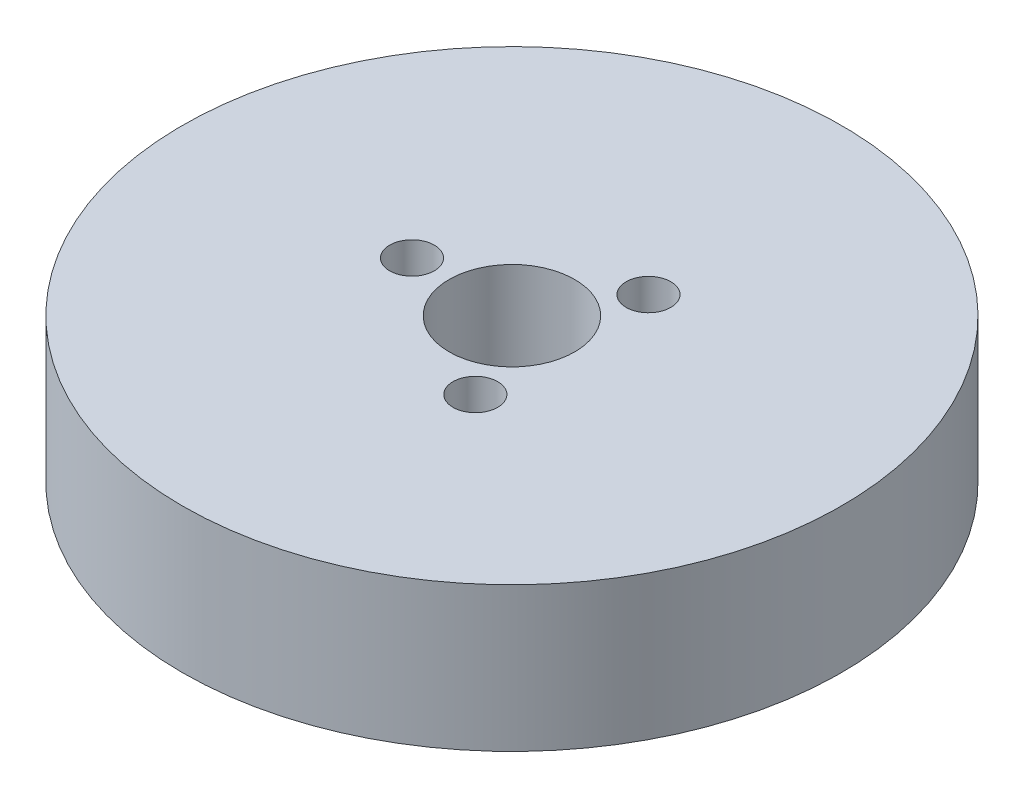
SolidWorks part; units mm, degrees
ref_plane "Front Plane" through (0, 0, 0) normal (0, 0, 1) x (1, 0, 0)
ref_plane "Top Plane" through (0, 0, 0) normal (0, 1, 0) x (1, 0, 0)
ref_plane "Right Plane" through (0, 0, 0) normal (1, 0, 0) x (0, 0, -1)
sketch "Sketch1" plane through (0, 0, 0) normal (0, 1, 0) x (1, 0, 0)
  circle A0 centre (0, 0) radius 52.5
  dimension "FLANGE_OD" = 105
extrude "Boss-Extrude1" add sketch "Sketch1" along normal blind 23
sketch "Sketch2" plane through (0, 0, 0) normal (0, 1, 0) x (1, 0, 0)
  circle A0 centre (0, 0) radius 10
  dimension "BORE_D" = 20
extrude "Cut-Extrude1" cut sketch "Sketch2" along normal through all
sketch "Sketch3" plane through (0, 23, 0) normal (0, 1, 0) x (1, 0, 0)
  circle A0 centre (0, 0) radius 15.9224 construction
  circle A1 centre (-15.9224, 0) radius 3.556
  dimension "BOLT_D" = 7.112
  dimension "BOLT_PCD" = 31.8449
extrude "Cut-Extrude2" cut sketch "Sketch3" against normal blind 13.802
pattern_circular "CirPattern1" count 3 over 360 about axis through (0, 0, 0) along (0, 1, 0) of "Cut-Extrude2"
